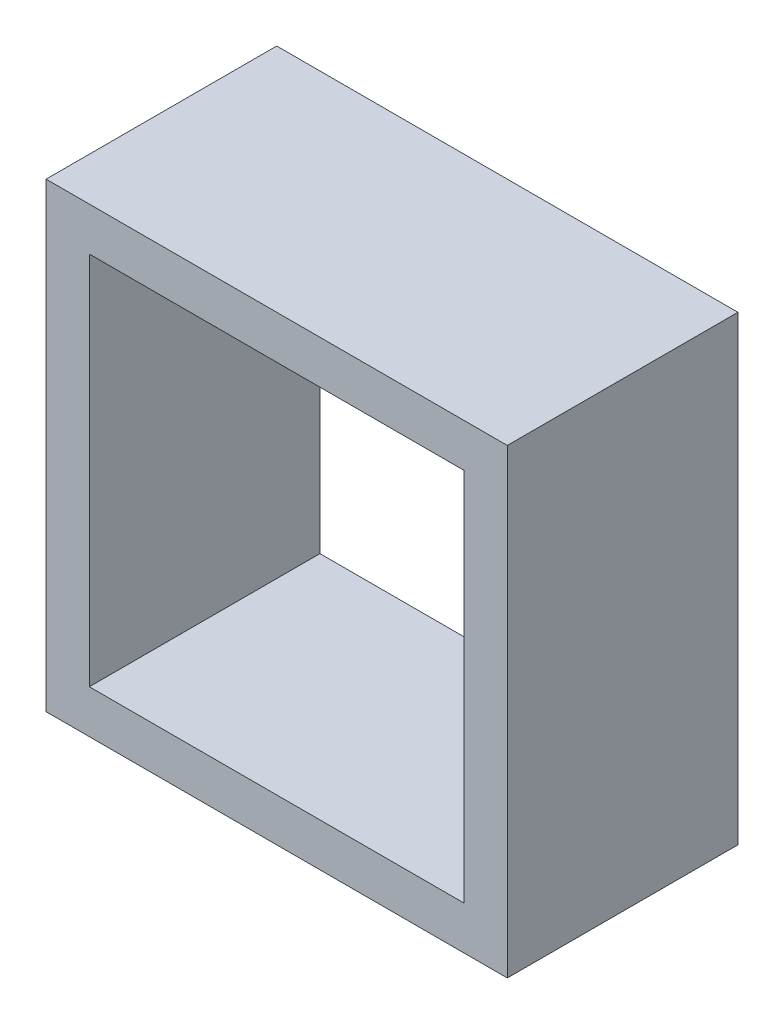
SolidWorks part; units mm, degrees
ref_plane "Plane1" through (0, 0, 0) normal (0, 0, 1) x (1, 0, 0)
ref_plane "Plane2" through (0, 0, 0) normal (0, 1, 0) x (1, 0, 0)
ref_plane "Plane3" through (0, 0, 0) normal (1, 0, 0) x (0, 0, -1)
sketch "Sketch1" plane through (0, 0, 0) normal (0, 0, 1) x (1, 0, 0)
  line L0 (4.7625, 4.7625) -> (4.7625, 46.0375)
  line L1 (46.0375, 46.0375) -> (4.7625, 46.0375)
  line L2 (46.0375, 46.0375) -> (46.0375, 4.7625)
  line L3 (4.7625, 4.7625) -> (46.0375, 4.7625)
  line L4 (0, 0) -> (50.8, 0)
  line L5 (0, 0) -> (0, 50.8)
  line L6 (50.8, 50.8) -> (0, 50.8)
  line L7 (50.8, 50.8) -> (50.8, 0)
  dimension "Thickness" = 4.7625
extrude "BaseTube" add sketch "Sketch1" along normal mid plane 25.4
